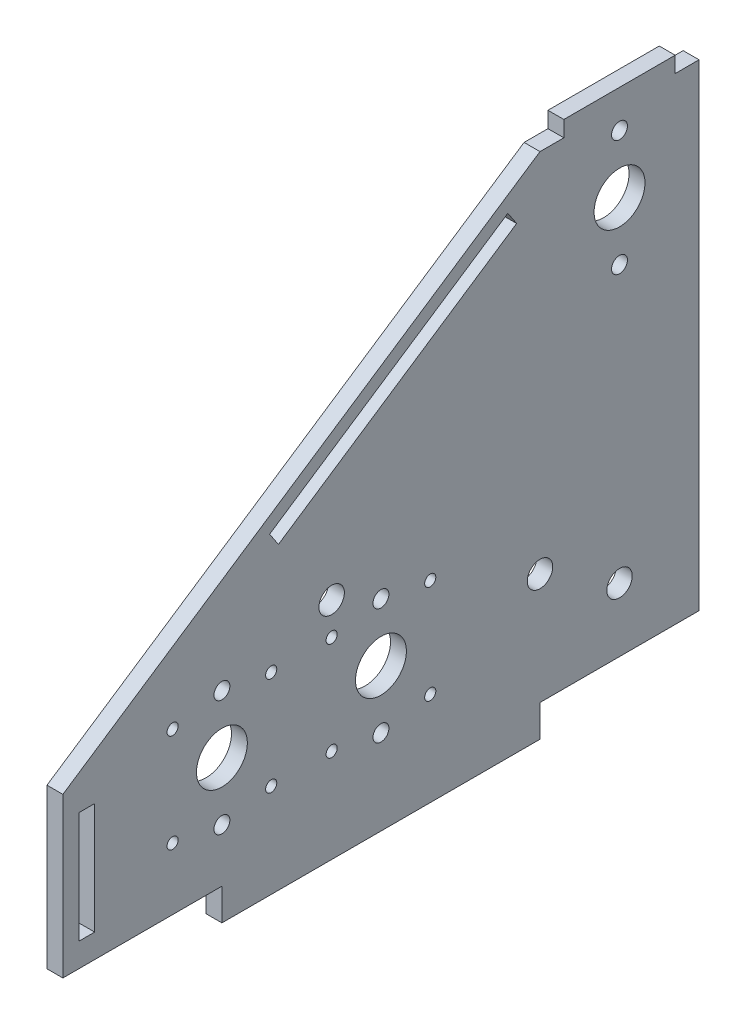
SolidWorks part; units mm, degrees
ref_plane "Alzado" through (0, 0, 0) normal (0, 0, 1) x (1, 0, 0)
ref_plane "Planta" through (0, 0, 0) normal (0, 1, 0) x (1, 0, 0)
ref_plane "Vista lateral" through (0, 0, 0) normal (1, 0, 0) x (0, 0, -1)
sketch "Croquis1" plane through (0, 0, 0) normal (1, 0, 0) x (0, 0, -1)
  line L0 (150, 150) -> (0, 50)
  line L1 (0, 0) -> (50, 0)
  line L2 (0, 0) -> (0, 50)
  line L3 (150, 150) -> (157.5, 150)
  line L4 (200, 0) -> (200, 150)
  line L5 (200, 75) -> (37.5, 75) construction
  line L6 (175, 155) -> (175, 0) construction
  line L7 (100, 116.6667) -> (100, -10) construction
  line L8 (84.5, 106.3333) -> (84.5, -10) construction
  line L9 (50, 0) -> (50, -10)
  line L10 (50, -10) -> (150, -10)
  line L11 (150, 0) -> (150, -10)
  line L12 (154, 35) -> (0, 35) construction
  line L13 (192.5, 150) -> (200, 150)
  line L14 (150, 0) -> (200, 0)
  line L15 (65, 88.3333) -> (139.8845, 138.2564)
  line L16 (157.5, 150) -> (157.5, 155)
  line L17 (157.5, 155) -> (192.5, 155)
  line L18 (192.5, 150) -> (192.5, 155)
  line L19 (139.8845, 138.2564) -> (142.658, 134.0961)
  line L20 (142.658, 134.0961) -> (67.7735, 84.1731)
  line L21 (67.7735, 84.1731) -> (65, 88.3333)
  line L22 (5, 53.3333) -> (5, 0) construction
  line L23 (65, 88.3333) -> (5, 48.3333) construction
  line L25 (5, 42.5) -> (10, 42.5)
  line L26 (5, 42.5) -> (5, 7.5)
  line L27 (5, 7.5) -> (10, 7.5)
  line L28 (10, 42.5) -> (10, 7.5)
  circle A0 centre (175, 125) radius 8
  circle A1 centre (175, 20) radius 4
  circle A2 centre (150, 35) radius 4
  circle A3 centre (175, 143.25) radius 2.5
  circle A4 centre (175, 106.75) radius 2.5
  circle A5 centre (100, 35) radius 8
  circle A6 centre (84.5, 60.6856) radius 4
  circle A7 centre (100, 53.25) radius 2.5
  circle A8 centre (100, 16.75) radius 2.5
  circle A9 centre (84.5, 50.5) radius 1.75
  circle A10 centre (115.5, 50.5) radius 1.75
  circle A11 centre (115.5, 19.5) radius 1.75
  circle A12 centre (84.5, 19.5) radius 1.75
  circle A13 centre (50, 35) radius 8
  circle A14 centre (50, 53.25) radius 2.5
  circle A15 centre (50, 16.75) radius 2.5
  circle A16 centre (34.5, 50.5) radius 1.75
  circle A17 centre (65.5, 50.5) radius 1.75
  circle A18 centre (65.5, 19.5) radius 1.75
  circle A19 centre (34.5, 19.5) radius 1.75
  dimension "D6" = 16
  dimension "D10" = 8
  dimension "D12" = 8
  dimension "D15" = 5
  dimension "D16" = 5
  dimension "D20" = 45
  dimension "D22" = 2
  dimension "D23" = 18.25
  dimension "D24" = 5
  dimension "D27" = 3.5
  dimension "D21" = 8
  dimension "D1" = 150
  dimension "D2" = 200
  dimension "D3" = 50
  dimension "D4" = 50
  dimension "D5" = 50
  dimension "D7" = 100
  dimension "D8" = 50
  dimension "D9" = 10
  dimension "D11" = 20
  dimension "D13" = 25
  dimension "D14" = 15
  dimension "D17" = 18.25
  dimension "D18" = 18.25
  dimension "D19" = 30
  dimension "D25" = 2
  dimension "D26" = 15.5
  dimension "D28" = 15.5
  dimension "D31" = 35
  dimension "D32" = 5
  dimension "D33" = 90
  dimension "D34" = 15
  dimension "D35" = 5
  dimension "D36" = 5
  dimension "D37" = 35
  dimension "D38" = 7.5
  dimension "D39" = 35
  dimension "D40" = 7.5
  dimension "D41" = 5
  dimension "D29" = 2
  dimension "D30" = 2
extrude "Saliente-Extruir1" add sketch "Croquis1" along normal blind 5
